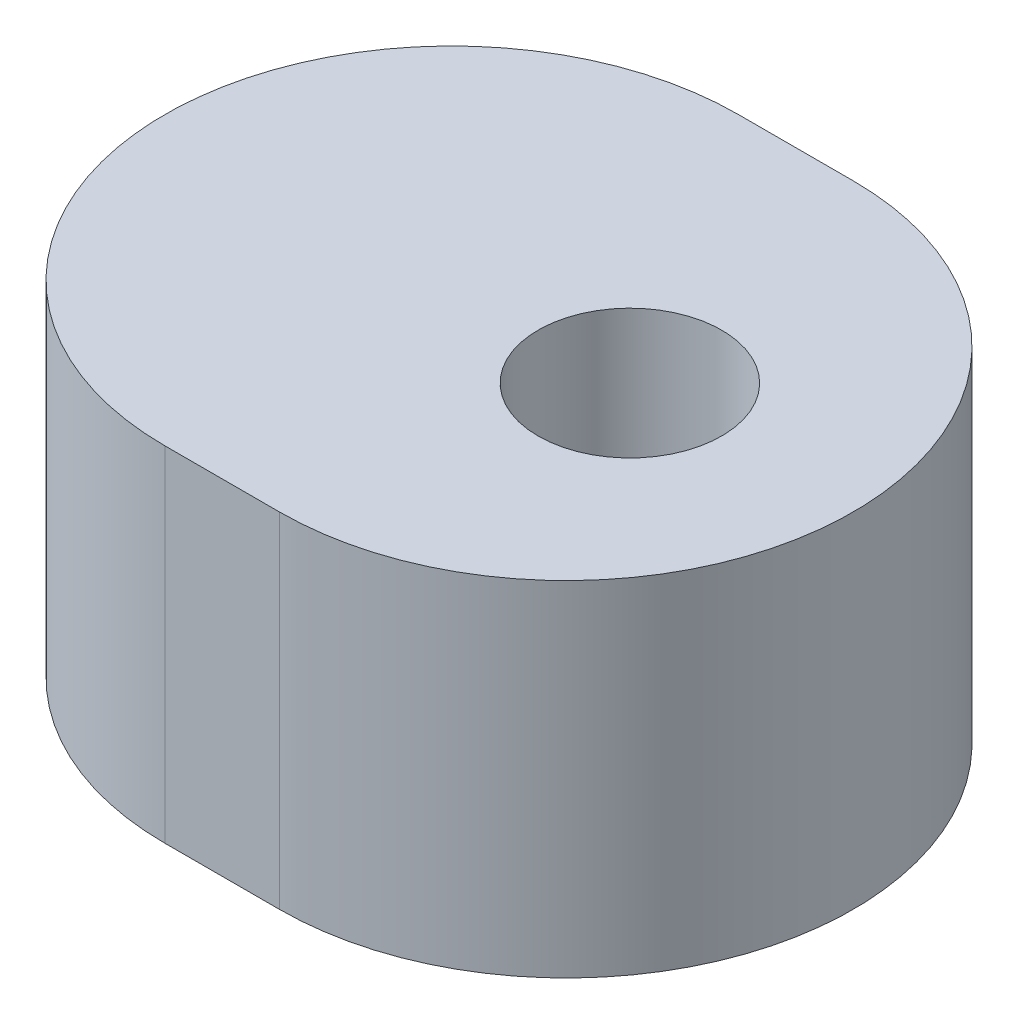
SolidWorks part; units mm, degrees
ref_plane "Plano frontal" through (0, 0, 0) normal (0, 0, 1) x (1, 0, 0)
ref_plane "Plano superior" through (0, 0, 0) normal (0, 1, 0) x (1, 0, 0)
ref_plane "Plano direito" through (0, 0, 0) normal (1, 0, 0) x (0, 0, -1)
ref_plane "Plano1" through (0, -18, 0) normal (0, -1, 0) x (1, 0, 0)
sketch "Esboço1" plane through (0, -18, 0) normal (0, -1, 0) x (1, 0, 0)
  line L0 (-3.1073, -5) -> (-1.1073, -5)
  line L1 (-1.1073, 5) -> (-3.1073, 5)
  line L2 (-2.1073, 5) -> (-2.1073, -5) construction
  line L3 (-2.1073, 0) -> (0, 0) construction
  circle A0 centre (0, 0) radius 1.6
  arc A1 (-3.1073, 5) -> (-3.1073, -5) centre (-3.1073, 0) ccw
  arc A2 (-1.1073, -5) -> (-1.1073, 5) centre (-1.1073, 0) ccw
  point P11 (0, 0)
  point P12 (0, 0)
  dimension "D1" = 3.2
  dimension "D2" = 5
  dimension "D4" = 2
  dimension "D3" = 3.1073
extrude "Ressalto-extrusão1" add sketch "Esboço1" against normal blind 6
